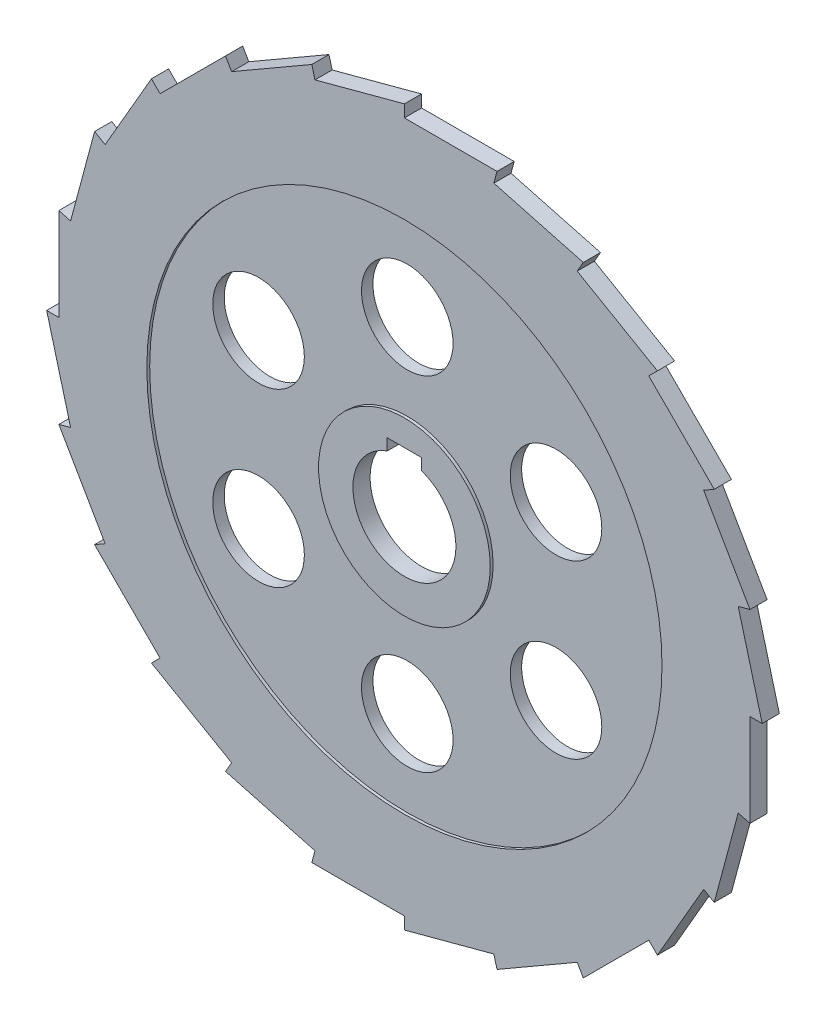
SolidWorks part; units mm, degrees
material "Alloy Steel"
ref_plane "Front Plane" through (0, 0, 0) normal (0, 0, 1) x (1, 0, 0)
ref_plane "Top Plane" through (0, 0, 0) normal (0, 1, 0) x (1, 0, 0)
ref_plane "Right Plane" through (0, 0, 0) normal (1, 0, 0) x (0, 0, -1)
sketch "Sketch1" plane through (0, 0, 0) normal (0, 0, 1) x (1, 0, 0)
  line L0 (0, 62.5) -> (0, 60.3704)
  line L1 (0, 60.3704) -> (16.1762, 60.3704)
  line L2 (15.625, 58.3133) -> (31.25, 54.1266)
  line L3 (16.1762, 60.3704) -> (15.625, 58.3133)
  line L4 (30.1852, 52.2823) -> (44.1942, 44.1942)
  line L5 (31.25, 54.1266) -> (30.1852, 52.2823)
  line L6 (42.6883, 42.6883) -> (54.1266, 31.25)
  line L7 (44.1942, 44.1942) -> (42.6883, 42.6883)
  line L8 (52.2823, 30.1852) -> (60.3704, 16.1762)
  line L9 (54.1266, 31.25) -> (52.2823, 30.1852)
  line L10 (58.3133, 15.625) -> (62.5, 0)
  line L11 (60.3704, 16.1762) -> (58.3133, 15.625)
  line L12 (60.3704, 0) -> (60.3704, -16.1762)
  line L13 (62.5, 0) -> (60.3704, 0)
  line L14 (58.3133, -15.625) -> (54.1266, -31.25)
  line L15 (60.3704, -16.1762) -> (58.3133, -15.625)
  line L16 (52.2823, -30.1852) -> (44.1942, -44.1942)
  line L17 (54.1266, -31.25) -> (52.2823, -30.1852)
  line L18 (42.6883, -42.6883) -> (31.25, -54.1266)
  line L19 (44.1942, -44.1942) -> (42.6883, -42.6883)
  line L20 (30.1852, -52.2823) -> (16.1762, -60.3704)
  line L21 (31.25, -54.1266) -> (30.1852, -52.2823)
  line L22 (15.625, -58.3133) -> (0, -62.5)
  line L23 (16.1762, -60.3704) -> (15.625, -58.3133)
  line L24 (0, -60.3704) -> (-16.1762, -60.3704)
  line L25 (0, -62.5) -> (0, -60.3704)
  line L26 (-15.625, -58.3133) -> (-31.25, -54.1266)
  line L27 (-16.1762, -60.3704) -> (-15.625, -58.3133)
  line L28 (-30.1852, -52.2823) -> (-44.1942, -44.1942)
  line L29 (-31.25, -54.1266) -> (-30.1852, -52.2823)
  line L30 (-42.6883, -42.6883) -> (-54.1266, -31.25)
  line L31 (-44.1942, -44.1942) -> (-42.6883, -42.6883)
  line L32 (-52.2823, -30.1852) -> (-60.3704, -16.1762)
  line L33 (-54.1266, -31.25) -> (-52.2823, -30.1852)
  line L34 (-58.3133, -15.625) -> (-62.5, 0)
  line L35 (-60.3704, -16.1762) -> (-58.3133, -15.625)
  line L36 (-60.3704, 0) -> (-60.3704, 16.1762)
  line L37 (-62.5, 0) -> (-60.3704, 0)
  line L38 (-58.3133, 15.625) -> (-54.1266, 31.25)
  line L39 (-60.3704, 16.1762) -> (-58.3133, 15.625)
  line L40 (-52.2823, 30.1852) -> (-44.1942, 44.1942)
  line L41 (-54.1266, 31.25) -> (-52.2823, 30.1852)
  line L42 (-42.6883, 42.6883) -> (-31.25, 54.1266)
  line L43 (-44.1942, 44.1942) -> (-42.6883, 42.6883)
  line L44 (-30.1852, 52.2823) -> (-16.1762, 60.3704)
  line L45 (-31.25, 54.1266) -> (-30.1852, 52.2823)
  line L46 (-15.625, 58.3133) -> (0, 62.5)
  line L47 (-16.1762, 60.3704) -> (-15.625, 58.3133)
  line L50 (-3, 8.4853) -> (-3, 10.4853)
  line L51 (-3, 10.4853) -> (3, 10.4853)
  line L52 (3, 8.4853) -> (3, 10.4853)
  line L53 (-3, 8.4853) -> (3, 10.4853) construction
  line L54 (-3, 10.4853) -> (3, 8.4853) construction
  circle A0 centre (0, 0) radius 62.5 construction
  circle A1 centre (0, 0) radius 45
  circle A2 centre (0, 0) radius 30 construction
  circle A3 centre (0, 30) radius 8
  circle A4 centre (25.9808, 15) radius 8
  circle A5 centre (25.9808, -15) radius 8
  circle A6 centre (0, -30) radius 8
  circle A7 centre (-25.9808, -15) radius 8
  circle A8 centre (-25.9808, 15) radius 8
  circle A9 centre (0, 0) radius 15
  arc A10 (-3, 8.4853) -> (3, 8.4853) centre (0, 0) ccw
  point P18 (0, 9)
  point P48 (0, 0)
  point P78 (0, 0)
  point P81 (0, 10.4853)
  dimension "D1" = 125
  dimension "D3" = 90
  dimension "D4" = 60
  dimension "D5" = 16
  dimension "D7" = 30
  dimension "D8" = 18
  dimension "D2" = 24
  dimension "D9" = 6
  dimension "D10" = 2
  dimension "D6" = 6
extrude "Boss-Extrude2" add sketch "Sketch1" along normal mid plane 3 contours L47 L44 L45 L42 L43 L40 L41 L38 L39 L36 L37 L34 L35 L32 L33 L30 L31 L28 L29 L26 L27 L24 L25 L22 L23 L20 L21 L18 L19 L16 L17 L14 L15 L12 L13 L10 L11 L8 L9 L6 L7 L4 L5 L2 L3 L1 L0 L46 A1 region at (-1.7678, 61.4352, 0)
extrude "Boss-Extrude3" add sketch "Sketch1<5>" along normal mid plane 2 contours A1 A9 A8 A7 A6 A5 A4 A3 region at (-43.7272, 0, 0)
sketch "Sketch1<5>" plane through (0, 0, 0) normal (0, 0, 1) x (1, 0, 0) same geometry as "Sketch1"
extrude "Boss-Extrude4" add sketch "Sketch1<6>" along normal mid plane 3 contours A9 A10 L50 L51 L52 region at (-14.5757, 0, 0)
sketch "Sketch1<6>" plane through (0, 0, 0) normal (0, 0, 1) x (1, 0, 0) same geometry as "Sketch1"
